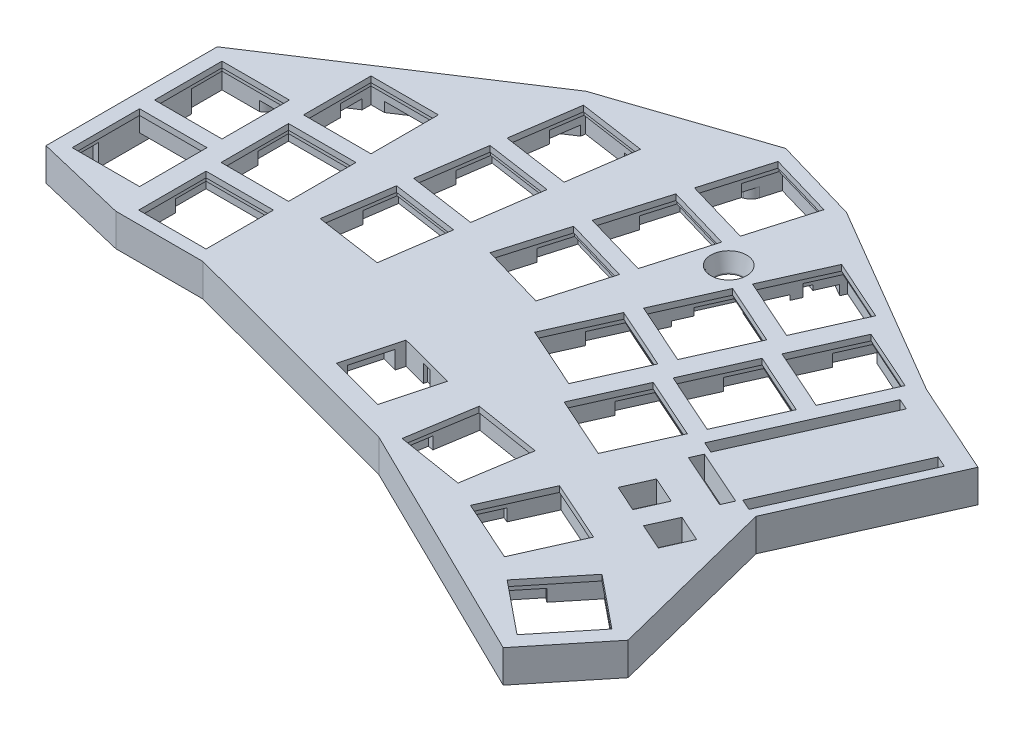
SolidWorks part; units mm, degrees
ref_plane "Front Plane" through (0, 0, 0) normal (0, 0, 1) x (1, 0, 0)
ref_plane "Top Plane" through (0, 0, 0) normal (0, 1, 0) x (1, 0, 0)
ref_plane "Right Plane" through (0, 0, 0) normal (1, 0, 0) x (0, 0, -1)
sketch "Ergogen Drawing" plane through (0, 0, 0) normal (0, 1, 0) x (1, 0, 0)
  line L0 (0.027, 17.9992) -> (18.027, 17.9992)
  line L1 (18.027, 17.9992) -> (18.027, -0.0008)
  line L2 (18.027, -0.0008) -> (0.027, -0.0008)
  line L3 (0.027, -0.0008) -> (0.027, 17.9992)
  line L4 (0.027, 34.9992) -> (18.027, 34.9992)
  line L5 (18.027, 34.9992) -> (18.027, 16.9992)
  line L6 (18.027, 16.9992) -> (0.027, 16.9992)
  line L7 (0.027, 16.9992) -> (0.027, 34.9992)
  line L8 (18.027, 15.9992) -> (36.027, 15.9992)
  line L9 (36.027, 15.9992) -> (36.027, -2.0008)
  line L10 (36.027, -2.0008) -> (18.027, -2.0008)
  line L11 (18.027, -2.0008) -> (18.027, 15.9992)
  line L12 (18.027, 32.9992) -> (36.027, 32.9992)
  line L13 (36.027, 32.9992) -> (36.027, 14.9992)
  line L14 (36.027, 14.9992) -> (18.027, 14.9992)
  line L15 (18.027, 14.9992) -> (18.027, 32.9992)
  line L16 (18.027, 49.9992) -> (36.027, 49.9992)
  line L17 (36.027, 49.9992) -> (36.027, 31.9992)
  line L18 (36.027, 31.9992) -> (18.027, 31.9992)
  line L19 (18.027, 31.9992) -> (18.027, 49.9992)
  line L20 (41.3768, 32.6051) -> (59.3329, 31.3495)
  line L21 (59.3329, 31.3495) -> (58.0773, 13.3933)
  line L22 (58.0773, 13.3933) -> (40.1211, 14.6489)
  line L23 (40.1211, 14.6489) -> (41.3768, 32.6051)
  line L24 (42.5626, 49.5637) -> (60.5188, 48.3081)
  line L25 (60.5188, 48.3081) -> (59.2631, 30.3519)
  line L26 (59.2631, 30.3519) -> (41.307, 31.6075)
  line L27 (41.307, 31.6075) -> (42.5626, 49.5637)
  line L28 (43.7485, 66.5223) -> (61.7046, 65.2667)
  line L29 (61.7046, 65.2667) -> (60.449, 47.3105)
  line L30 (60.449, 47.3105) -> (42.4929, 48.5661)
  line L31 (42.4929, 48.5661) -> (43.7485, 66.5223)
  line L32 (66.0898, 43.7082) -> (83.8507, 40.7838)
  line L33 (83.8507, 40.7838) -> (80.9263, 23.023)
  line L34 (80.9263, 23.023) -> (63.1655, 25.9473)
  line L35 (63.1655, 25.9473) -> (66.0898, 43.7082)
  line L36 (68.8517, 60.4823) -> (86.6126, 57.558)
  line L37 (86.6126, 57.558) -> (83.6882, 39.7971)
  line L38 (83.6882, 39.7971) -> (65.9274, 42.7215)
  line L39 (65.9274, 42.7215) -> (68.8517, 60.4823)
  line L40 (71.6136, 77.2565) -> (89.3745, 74.3321)
  line L41 (89.3745, 74.3321) -> (86.4501, 56.5713)
  line L42 (86.4501, 56.5713) -> (68.6893, 59.4956)
  line L43 (68.6893, 59.4956) -> (71.6136, 77.2565)
  line L44 (88.5581, 32.769) -> (105.9366, 28.0799)
  line L45 (105.9366, 28.0799) -> (101.2475, 10.7014)
  line L46 (101.2475, 10.7014) -> (83.869, 15.3905)
  line L47 (83.869, 15.3905) -> (88.5581, 32.769)
  line L48 (92.9866, 49.182) -> (110.3652, 44.4929)
  line L49 (110.3652, 44.4929) -> (105.6761, 27.1144)
  line L50 (105.6761, 27.1144) -> (88.2976, 31.8035)
  line L51 (88.2976, 31.8035) -> (92.9866, 49.182)
  line L52 (97.4152, 65.595) -> (114.7937, 60.906)
  line L53 (114.7937, 60.906) -> (110.1046, 43.5274)
  line L54 (110.1046, 43.5274) -> (92.7261, 48.2165)
  line L55 (92.7261, 48.2165) -> (97.4152, 65.595)
  line L56 (107.0448, 26.9674) -> (124.0477, 21.0597)
  line L57 (124.0477, 21.0597) -> (118.14, 4.0568)
  line L58 (118.14, 4.0568) -> (101.1371, 9.9645)
  line L59 (101.1371, 9.9645) -> (107.0448, 26.9674)
  line L60 (112.6243, 43.0257) -> (129.6273, 37.118)
  line L61 (129.6273, 37.118) -> (123.7195, 20.1151)
  line L62 (123.7195, 20.1151) -> (106.7166, 26.0228)
  line L63 (106.7166, 26.0228) -> (112.6243, 43.0257)
  line L64 (118.2039, 59.084) -> (135.2068, 53.1763)
  line L65 (135.2068, 53.1763) -> (129.299, 36.1734)
  line L66 (129.299, 36.1734) -> (112.2961, 42.0811)
  line L67 (112.2961, 42.0811) -> (118.2039, 59.084)
  line L68 (95.4197, 6.4051) -> (112.5714, 0.9445)
  line L69 (112.5714, 0.9445) -> (107.1108, -16.2072)
  line L70 (107.1108, -16.2072) -> (89.959, -10.7466)
  line L71 (89.959, -10.7466) -> (95.4197, 6.4051)
  line L72 (116.0129, -0.5249) -> (131.9353, -8.9198)
  line L73 (131.9353, -8.9198) -> (123.5404, -24.8423)
  line L74 (123.5404, -24.8423) -> (107.6179, -16.4473)
  line L75 (107.6179, -16.4473) -> (116.0129, -0.5249)
  line L76 (135.0644, -10.9721) -> (149.2602, -22.0392)
  line L77 (149.2602, -22.0392) -> (138.1931, -36.235)
  line L78 (138.1931, -36.235) -> (123.9973, -25.1679)
  line L79 (123.9973, -25.1679) -> (135.0644, -10.9721)
sketch "Layout Based on OG" plane through (0, 0, 0) normal (0, 1, 0) x (1, 0, 0)
  line L0 (0, 0) -> (0, 17) construction
  line L1 (0, 17) -> (18, 17) construction
  line L2 (18, 17) -> (18, 0) construction
  line L3 (18, 0) -> (0, 0) construction
  line L4 (2.05, 1.55) -> (2.05, 15.45)
  line L5 (2.05, 15.45) -> (15.95, 15.45)
  line L6 (15.95, 15.45) -> (15.95, 1.55)
  line L7 (15.95, 1.55) -> (2.05, 1.55)
  line L8 (109.1798, 58.6066) -> (27, -125.5436) construction
  line L9 (27, 46.7087) -> (27, -125.5436) construction
  line L10 (84.3863, 71.4039) -> (27, -125.5436) construction
  line L11 (54.2678, 62.3831) -> (27, -125.5436) construction
  line L12 (44.7261, 45.0233) -> (58.4821, 43.0274)
  line L13 (2.05, 18.55) -> (15.95, 18.55)
  line L14 (2.05, 18.55) -> (2.05, 32.45)
  line L15 (2.05, 32.45) -> (15.95, 32.45)
  line L16 (15.95, 18.55) -> (15.95, 32.45)
  line L17 (20.05, 31.2587) -> (33.95, 31.2587)
  line L18 (20.05, 31.2587) -> (20.05, 45.1587)
  line L19 (20.05, 45.1587) -> (33.95, 45.1587)
  line L20 (33.95, 31.2587) -> (33.95, 45.1587)
  line L21 (33.95, 28.1587) -> (20.05, 28.1587)
  line L22 (33.95, 28.1587) -> (33.95, 14.2587)
  line L23 (33.95, 14.2587) -> (20.05, 14.2587)
  line L24 (20.05, 28.1587) -> (20.05, 14.2587)
  line L25 (20.05, -2.7413) -> (33.95, -2.7413)
  line L26 (20.05, -2.7413) -> (20.05, 11.1587)
  line L27 (20.05, 11.1587) -> (33.95, 11.1587)
  line L28 (33.95, -2.7413) -> (33.95, 11.1587)
  line L29 (44.7261, 45.0233) -> (42.7302, 31.2674)
  line L30 (58.4821, 43.0274) -> (56.4861, 29.2714)
  line L31 (42.7302, 31.2674) -> (56.4861, 29.2714)
  line L32 (42.285, 28.1995) -> (56.041, 26.2036)
  line L33 (42.285, 28.1995) -> (40.2891, 14.4436)
  line L34 (56.041, 26.2036) -> (54.045, 12.4476)
  line L35 (40.2891, 14.4436) -> (54.045, 12.4476)
  line L36 (47.1672, 61.8472) -> (60.9232, 59.8512)
  line L37 (47.1672, 61.8472) -> (45.1712, 48.0912)
  line L38 (60.9232, 59.8512) -> (58.9272, 46.0953)
  line L39 (45.1712, 48.0912) -> (58.9272, 46.0953)
  line L40 (77.2802, 71.86) -> (90.6252, 67.9716)
  line L41 (77.2802, 71.86) -> (73.3917, 58.515)
  line L42 (90.6252, 67.9716) -> (86.7368, 54.6265)
  line L43 (73.3917, 58.515) -> (86.7368, 54.6265)
  line L44 (85.8695, 51.6503) -> (72.5245, 55.5388)
  line L45 (85.8695, 51.6503) -> (81.9811, 38.3053)
  line L46 (72.5245, 55.5388) -> (68.6361, 42.1937)
  line L47 (81.9811, 38.3053) -> (68.6361, 42.1937)
  line L48 (67.7688, 39.2175) -> (81.1139, 35.329)
  line L49 (67.7688, 39.2175) -> (63.8804, 25.8725)
  line L50 (81.1139, 35.329) -> (77.2254, 21.984)
  line L51 (63.8804, 25.8725) -> (77.2254, 21.984)
  line L52 (102.2015, 60.0235) -> (114.8949, 54.3589)
  line L53 (102.2015, 60.0235) -> (96.5369, 47.3301)
  line L54 (114.8949, 54.3589) -> (109.2302, 41.6655)
  line L55 (96.5369, 47.3301) -> (109.2302, 41.6655)
  line L56 (107.9669, 38.8346) -> (95.2735, 44.4992)
  line L57 (107.9669, 38.8346) -> (102.3023, 26.1412)
  line L58 (95.2735, 44.4992) -> (89.6089, 31.8058)
  line L59 (102.3023, 26.1412) -> (89.6089, 31.8058)
  line L60 (101.039, 23.3103) -> (88.3456, 28.9749)
  line L61 (101.039, 23.3103) -> (95.3744, 10.6169)
  line L62 (88.3456, 28.9749) -> (82.681, 16.2815)
  line L63 (95.3744, 10.6169) -> (82.681, 16.2815)
  line L64 (117.7053, 50.5958) -> (130.3987, 44.9312)
  line L65 (117.7053, 50.5958) -> (112.0407, 37.9024)
  line L66 (130.3987, 44.9312) -> (124.734, 32.2378)
  line L67 (112.0407, 37.9024) -> (124.734, 32.2378)
  line L68 (123.4707, 29.4069) -> (110.7773, 35.0715)
  line L69 (123.4707, 29.4069) -> (117.8061, 16.7135)
  line L70 (110.7773, 35.0715) -> (105.1127, 22.3782)
  line L71 (117.8061, 16.7135) -> (105.1127, 22.3782)
  line L72 (116.5428, 13.8826) -> (103.8494, 19.5473)
  line L73 (116.5428, 13.8826) -> (110.8782, 1.1892)
  line L74 (103.8494, 19.5473) -> (98.1848, 6.8539)
  line L75 (110.8782, 1.1892) -> (98.1848, 6.8539)
  line L76 (90.1692, -2.6429) -> (103.8962, -4.8292)
  line L77 (90.1692, -2.6429) -> (87.9829, -16.3699)
  line L78 (103.8962, -4.8292) -> (101.7099, -18.5562)
  line L79 (87.9829, -16.3699) -> (101.7099, -18.5562)
  line L80 (112.6329, -8.5638) -> (125.3263, -14.2284)
  line L81 (112.6329, -8.5638) -> (106.9683, -21.2572)
  line L82 (125.3263, -14.2284) -> (119.6617, -26.9218)
  line L83 (106.9683, -21.2572) -> (119.6617, -26.9218)
  line L84 (132.8305, -19.9983) -> (143.6253, -28.7552)
  line L85 (132.8305, -19.9983) -> (124.0737, -30.7931)
  line L86 (143.6253, -28.7552) -> (134.8684, -39.55)
  line L87 (124.0737, -30.7931) -> (134.8684, -39.55)
  line L88 (0, 0) -> (0, 34) construction
  line L89 (0, 34) -> (18, 46.7087) construction
  line L90 (18, 46.7087) -> (45.361, 63.6755) construction
  line L91 (45.361, 63.6755) -> (75.7456, 73.9216) construction
  line L92 (75.7456, 73.9216) -> (93.027, 68.8862) construction
  line L93 (93.027, 68.8862) -> (117.3986, 54.9389) construction
  line L94 (117.3986, 54.9389) -> (132.9024, 45.5112) construction
  line L95 (146.1938, -28.843) -> (135.484, -42.0452) construction
  line L96 (135.484, -42.0452) -> (85.7146, -17.5782) construction
  line L97 (0, 0) -> (18, -4.2913) construction
  line L98 (132.9024, 45.5112) -> (119.0465, 14.4627) construction
  line L99 (18, -4.2913) -> (36, -4.2913) construction
  line L100 (36, -4.2913) -> (85.7146, -17.5782) construction
  line L101 (119.0465, 14.4627) -> (137.3104, 6.3121) construction
  line L102 (137.3104, 6.3121) -> (151.1662, 37.3607) construction
  line L103 (151.1662, 37.3607) -> (132.9024, 45.5112) construction
  line L104 (146.1938, -28.843) -> (137.3104, 6.3121) construction
  line L105 (137.3104, 6.3121) -> (151.1662, 37.3607) construction
  line L106 (151.1662, 37.3607) -> (132.9024, 45.5112) construction
  line L107 (119.9597, 14.0551) -> (132.3892, 41.9075)
  line L108 (132.3892, 41.9075) -> (134.6722, 40.8887)
  line L109 (134.6722, 40.8887) -> (122.2427, 13.0363)
  line L110 (122.2427, 13.0363) -> (119.9597, 14.0551)
  line L111 (136.3972, 6.7197) -> (148.8267, 34.5721)
  line L112 (148.8267, 34.5721) -> (146.5437, 35.5909)
  line L113 (146.5437, 35.5909) -> (134.1142, 7.7385)
  line L114 (134.1142, 7.7385) -> (136.3972, 6.7197)
  line L115 (79.4058, -12.7868) -> (67.8127, -9.6883)
  line L116 (67.8127, -9.6883) -> (70.8336, 1.6149)
  line L117 (70.8336, 1.6149) -> (82.4267, -1.4835)
  line L118 (82.4267, -1.4835) -> (79.4058, -12.7868)
  line L119 (97.0327, -3.7361) -> (94.8464, -17.4631) construction
  line L120 (118.9913, -2.8379) -> (121.4364, 2.6412)
  line L121 (121.4364, 2.6412) -> (126.9156, 0.1961)
  line L122 (76.6302, 0.0657) -> (73.6092, -11.2375) construction
  line L123 (126.9156, 0.1961) -> (124.4704, -5.2831)
  line L124 (124.4704, -5.2831) -> (118.9913, -2.8379)
  line L125 (128.4611, -7.064) -> (130.9062, -1.5848)
  line L126 (130.9062, -1.5848) -> (136.3854, -4.03)
  line L127 (136.3854, -4.03) -> (133.9402, -9.5091)
  line L128 (133.9402, -9.5091) -> (128.4611, -7.064)
  line L137 (124.176, 1.4187) -> (121.7308, -4.0605) construction
  line L138 (133.6458, -2.8074) -> (131.2006, -8.2865) construction
  line L139 (126.7317, 7.1456) -> (128.1784, 10.3874) construction
  line L140 (135.0103, 42.8732) -> (147.795, 37.1678) construction
  line L141 (147.795, 37.1678) -> (133.1241, 4.2929) construction
  line L142 (133.1241, 4.2929) -> (120.3393, 9.9982) construction
  line L143 (120.3393, 9.9982) -> (135.0103, 42.8732) construction
  line L144 (120.9329, 9.7333) -> (121.9517, 12.0163)
  line L145 (121.9517, 12.0163) -> (133.5493, 6.8407)
  line L146 (133.5493, 6.8407) -> (132.5305, 4.5578)
  line L147 (132.5305, 4.5578) -> (120.9329, 9.7333)
  line L148 (126.9156, 0.1961) -> (140.3735, -5.8097) construction
  line L164 (-1, 34.5181) -> (-1, -0.7896)
  line L165 (-1, -0.7896) -> (17.8824, -5.2913)
  line L166 (17.8824, -5.2913) -> (35.8687, -5.2913)
  line L167 (35.8687, -5.2913) -> (85.3615, -18.5189)
  line L168 (85.3615, -18.5189) -> (135.7583, -43.2944)
  line L169 (135.7583, -43.2944) -> (147.2861, -29.0838)
  line L170 (147.2861, -29.0838) -> (138.3648, 6.2211)
  line L171 (138.3648, 6.2211) -> (152.487, 37.8664)
  line L172 (152.487, 37.8664) -> (133.3678, 46.3986)
  line L173 (133.3678, 46.3986) -> (117.9068, 55.8002) construction
  line L174 (117.9068, 55.8002) -> (93.4207, 69.8131) construction
  line L175 (93.4207, 69.8131) -> (75.7238, 74.9696)
  line L176 (75.7238, 74.9696) -> (44.9321, 64.5862)
  line L177 (44.9321, 64.5862) -> (17.4476, 47.5429) construction
  line L178 (17.4476, 47.5429) -> (-1, 34.5181) construction
  line L179 (-1, 34.5181) -> (44.9321, 64.5862)
  line L180 (133.3678, 46.3986) -> (93.4207, 69.8131)
  line L181 (27, -125.5436) -> (90.7493, 48.2155) construction
  circle A0 centre (142.6577, -23.0128) radius 2 construction
  circle A1 centre (142.6577, -23.0128) radius 1
  circle A2 centre (99.1237, -21.9416) radius 2 construction
  circle A3 centre (99.1237, -21.9416) radius 1
  circle A6 centre (16.2, -1.8061) radius 2 construction
  circle A7 centre (16.2, -1.8061) radius 1
  circle A8 centre (7.0467, 36.2) radius 2 construction
  circle A9 centre (7.0467, 36.2) radius 1
  circle A10 centre (72.7535, 70.802) radius 2 construction
  circle A11 centre (72.7535, 70.802) radius 1
  circle A12 centre (144.6437, 38.0814) radius 2 construction
  circle A13 centre (144.6437, 38.0814) radius 1
  circle A14 centre (90.7493, 48.2155) radius 3
  point P10 (110.8277, 18.1304)
  point P11 (117.7557, 33.6547)
  point P128 (75.1197, -5.5859)
  point P129 (95.9395, -10.5996)
  point P146 (127.7505, 9.4285)
  point P148 (128.1784, 10.3874)
  point P150 (122.9534, -1.3209)
  point P186 (0, 0)
  line B0 (18, 29.7087) -> (18, 46.7087) construction
  line B1 (18, 46.7087) -> (36, 46.7087) construction
  line B2 (36, 46.7087) -> (36, 29.7087) construction
  line B3 (36, 29.7087) -> (18, 29.7087) construction
  line B4 (20.05, 31.2587) -> (20.05, 45.1587) construction
  line B5 (20.05, 45.1587) -> (33.95, 45.1587) construction
  line B6 (33.95, 45.1587) -> (33.95, 31.2587) construction
  line B7 (33.95, 31.2587) -> (20.05, 31.2587) construction
  line B8 (18, 12.7087) -> (18, 29.7087) construction
  line B9 (18, 29.7087) -> (36, 29.7087) construction
  line B10 (36, 29.7087) -> (36, 12.7087) construction
  line B11 (36, 12.7087) -> (18, 12.7087) construction
  line B12 (20.05, 14.2587) -> (20.05, 28.1587) construction
  line B13 (20.05, 28.1587) -> (33.95, 28.1587) construction
  line B14 (33.95, 28.1587) -> (33.95, 14.2587) construction
  line B15 (33.95, 14.2587) -> (20.05, 14.2587) construction
  line B16 (18, -4.2913) -> (18, 12.7087) construction
  line B17 (18, 12.7087) -> (36, 12.7087) construction
  line B18 (36, 12.7087) -> (36, -4.2913) construction
  line B19 (36, -4.2913) -> (18, -4.2913) construction
  line B20 (20.05, -2.7413) -> (20.05, 11.1587) construction
  line B21 (20.05, 11.1587) -> (33.95, 11.1587) construction
  line B22 (33.95, 11.1587) -> (33.95, -2.7413) construction
  line B23 (33.95, -2.7413) -> (20.05, -2.7413) construction
  line B24 (42.9199, 46.8516) -> (45.361, 63.6755) construction
  line B25 (45.361, 63.6755) -> (63.1745, 61.0908) construction
  line B26 (63.1745, 61.0908) -> (60.7334, 44.267) construction
  line B27 (60.7334, 44.267) -> (42.9199, 46.8516) construction
  line B28 (45.1712, 48.0912) -> (47.1672, 61.8472) construction
  line B29 (47.1672, 61.8472) -> (60.9232, 59.8512) construction
  line B30 (60.9232, 59.8512) -> (58.9272, 46.0953) construction
  line B31 (58.9272, 46.0953) -> (45.1712, 48.0912) construction
  line B32 (40.4788, 30.0278) -> (42.9199, 46.8516) construction
  line B33 (42.9199, 46.8516) -> (60.7334, 44.267) construction
  line B34 (60.7334, 44.267) -> (58.2923, 27.4431) construction
  line B35 (58.2923, 27.4431) -> (40.4788, 30.0278) construction
  line B36 (42.7302, 31.2674) -> (44.7261, 45.0233) construction
  line B37 (44.7261, 45.0233) -> (58.4821, 43.0274) construction
  line B38 (58.4821, 43.0274) -> (56.4861, 29.2714) construction
  line B39 (56.4861, 29.2714) -> (42.7302, 31.2674) construction
  line B40 (38.0377, 13.204) -> (40.4788, 30.0278) construction
  line B41 (40.4788, 30.0278) -> (58.2923, 27.4431) construction
  line B42 (58.2923, 27.4431) -> (55.8512, 10.6193) construction
  line B43 (55.8512, 10.6193) -> (38.0377, 13.204) construction
  line B44 (40.2891, 14.4436) -> (42.285, 28.1995) construction
  line B45 (42.285, 28.1995) -> (56.041, 26.2036) construction
  line B46 (56.041, 26.2036) -> (54.045, 12.4476) construction
  line B47 (54.045, 12.4476) -> (40.2891, 14.4436) construction
  line B48 (70.99, 57.6004) -> (75.7456, 73.9216) construction
  line B49 (75.7456, 73.9216) -> (93.027, 68.8862) construction
  line B50 (93.027, 68.8862) -> (88.2713, 52.5649) construction
  line B51 (88.2713, 52.5649) -> (70.99, 57.6004) construction
  line B52 (73.3917, 58.515) -> (77.2802, 71.86) construction
  line B53 (77.2802, 71.86) -> (90.6252, 67.9716) construction
  line B54 (90.6252, 67.9716) -> (86.7368, 54.6265) construction
  line B55 (86.7368, 54.6265) -> (73.3917, 58.515) construction
  line B56 (66.2343, 41.2791) -> (70.99, 57.6004) construction
  line B57 (70.99, 57.6004) -> (88.2713, 52.5649) construction
  line B58 (88.2713, 52.5649) -> (83.5156, 36.2437) construction
  line B59 (83.5156, 36.2437) -> (66.2343, 41.2791) construction
  line B60 (68.6361, 42.1937) -> (72.5245, 55.5388) construction
  line B61 (72.5245, 55.5388) -> (85.8695, 51.6503) construction
  line B62 (85.8695, 51.6503) -> (81.9811, 38.3053) construction
  line B63 (81.9811, 38.3053) -> (68.6361, 42.1937) construction
  line B64 (61.4786, 24.9578) -> (66.2343, 41.2791) construction
  line B65 (66.2343, 41.2791) -> (83.5156, 36.2437) construction
  line B66 (83.5156, 36.2437) -> (78.76, 19.9224) construction
  line B67 (78.76, 19.9224) -> (61.4786, 24.9578) construction
  line B68 (63.8804, 25.8725) -> (67.7688, 39.2175) construction
  line B69 (67.7688, 39.2175) -> (81.1139, 35.329) construction
  line B70 (81.1139, 35.329) -> (77.2254, 21.984) construction
  line B71 (77.2254, 21.984) -> (63.8804, 25.8725) construction
  line B72 (80.1772, 15.7015) -> (87.1052, 31.2258) construction
  line B73 (87.1052, 31.2258) -> (103.5427, 23.8903) construction
  line B74 (103.5427, 23.8903) -> (96.6147, 8.366) construction
  line B75 (96.6147, 8.366) -> (80.1772, 15.7015) construction
  line B76 (82.681, 16.2815) -> (88.3456, 28.9749) construction
  line B77 (88.3456, 28.9749) -> (101.039, 23.3103) construction
  line B78 (101.039, 23.3103) -> (95.3744, 10.6169) construction
  line B79 (95.3744, 10.6169) -> (82.681, 16.2815) construction
  line B80 (87.1052, 31.2258) -> (94.0331, 46.7501) construction
  line B81 (94.0331, 46.7501) -> (110.4706, 39.4146) construction
  line B82 (110.4706, 39.4146) -> (103.5427, 23.8903) construction
  line B83 (103.5427, 23.8903) -> (87.1052, 31.2258) construction
  line B84 (89.6089, 31.8058) -> (95.2735, 44.4992) construction
  line B85 (95.2735, 44.4992) -> (107.9669, 38.8346) construction
  line B86 (107.9669, 38.8346) -> (102.3023, 26.1412) construction
  line B87 (102.3023, 26.1412) -> (89.6089, 31.8058) construction
  line B88 (94.0331, 46.7501) -> (100.9611, 62.2744) construction
  line B89 (100.9611, 62.2744) -> (117.3986, 54.9389) construction
  line B90 (117.3986, 54.9389) -> (110.4706, 39.4146) construction
  line B91 (110.4706, 39.4146) -> (94.0331, 46.7501) construction
  line B92 (96.5369, 47.3301) -> (102.2015, 60.0235) construction
  line B93 (102.2015, 60.0235) -> (114.8949, 54.3589) construction
  line B94 (114.8949, 54.3589) -> (109.2302, 41.6655) construction
  line B95 (109.2302, 41.6655) -> (96.5369, 47.3301) construction
  line B96 (109.5369, 37.3224) -> (116.4649, 52.8467) construction
  line B97 (116.4649, 52.8467) -> (132.9024, 45.5112) construction
  line B98 (132.9024, 45.5112) -> (125.9744, 29.9869) construction
  line B99 (125.9744, 29.9869) -> (109.5369, 37.3224) construction
  line B100 (112.0407, 37.9024) -> (117.7053, 50.5958) construction
  line B101 (117.7053, 50.5958) -> (130.3987, 44.9312) construction
  line B102 (130.3987, 44.9312) -> (124.734, 32.2378) construction
  line B103 (124.734, 32.2378) -> (112.0407, 37.9024) construction
  line B104 (102.609, 21.7981) -> (109.5369, 37.3224) construction
  line B105 (109.5369, 37.3224) -> (125.9744, 29.9869) construction
  line B106 (125.9744, 29.9869) -> (119.0465, 14.4627) construction
  line B107 (119.0465, 14.4627) -> (102.609, 21.7981) construction
  line B108 (105.1127, 22.3782) -> (110.7773, 35.0715) construction
  line B109 (110.7773, 35.0715) -> (123.4707, 29.4069) construction
  line B110 (123.4707, 29.4069) -> (117.8061, 16.7135) construction
  line B111 (117.8061, 16.7135) -> (105.1127, 22.3782) construction
  line B112 (95.6811, 6.2738) -> (102.609, 21.7981) construction
  line B113 (102.609, 21.7981) -> (119.0465, 14.4627) construction
  line B114 (119.0465, 14.4627) -> (112.1185, -1.0616) construction
  line B115 (112.1185, -1.0616) -> (95.6811, 6.2738) construction
  line B116 (98.1848, 6.8539) -> (103.8494, 19.5473) construction
  line B117 (103.8494, 19.5473) -> (116.5428, 13.8826) construction
  line B118 (116.5428, 13.8826) -> (110.8782, 1.1892) construction
  line B119 (110.8782, 1.1892) -> (98.1848, 6.8539) construction
  line B120 (104.4646, -21.8372) -> (111.3925, -6.3129) construction
  line B121 (111.3925, -6.3129) -> (127.83, -13.6484) construction
  line B122 (127.83, -13.6484) -> (120.9021, -29.1727) construction
  line B123 (120.9021, -29.1727) -> (104.4646, -21.8372) construction
  line B124 (106.9683, -21.2572) -> (112.6329, -8.5638) construction
  line B125 (112.6329, -8.5638) -> (125.3263, -14.2284) construction
  line B126 (125.3263, -14.2284) -> (119.6617, -26.9218) construction
  line B127 (119.6617, -26.9218) -> (106.9683, -21.2572) construction
  line B128 (85.7146, -17.5782) -> (88.3885, -0.7898) construction
  line B129 (88.3885, -0.7898) -> (106.1645, -3.621) construction
  line B130 (106.1645, -3.621) -> (103.4906, -20.4094) construction
  line B131 (103.4906, -20.4094) -> (85.7146, -17.5782) construction
  line B132 (87.9829, -16.3699) -> (90.1692, -2.6429) construction
  line B133 (90.1692, -2.6429) -> (103.8962, -4.8292) construction
  line B134 (103.8962, -4.8292) -> (101.7099, -18.5562) construction
  line B135 (101.7099, -18.5562) -> (87.9829, -16.3699) construction
  line B136 (121.5051, -30.7054) -> (132.215, -17.5031) construction
  line B137 (132.215, -17.5031) -> (146.1938, -28.843) construction
  line B138 (146.1938, -28.843) -> (135.484, -42.0452) construction
  line B139 (135.484, -42.0452) -> (121.5051, -30.7054) construction
  line B140 (124.0737, -30.7931) -> (132.8305, -19.9983) construction
  line B141 (132.8305, -19.9983) -> (143.6253, -28.7552) construction
  line B142 (143.6253, -28.7552) -> (134.8684, -39.55) construction
  line B143 (134.8684, -39.55) -> (124.0737, -30.7931) construction
  line B144 (0, 17) -> (0, 34) construction
  line B145 (0, 34) -> (18, 34) construction
  line B146 (18, 34) -> (18, 17) construction
  line B147 (18, 17) -> (0, 17) construction
  line B148 (2.05, 18.55) -> (2.05, 32.45) construction
  line B149 (2.05, 32.45) -> (15.95, 32.45) construction
  line B150 (15.95, 32.45) -> (15.95, 18.55) construction
  line B151 (15.95, 18.55) -> (2.05, 18.55) construction
  dimension "D46" = 4
  dimension "D47" = 2
  dimension "D48" = 3
  dimension "D52" = 4
  dimension "D53" = 2
  dimension "D54" = 4
  dimension "D55" = 2
  dimension "D57" = 4
  dimension "D58" = 2
  dimension "D60" = 4
  dimension "D61" = 2
  dimension "D63" = 4
  dimension "D64" = 2
  dimension "D51" = 3.85
  dimension "D83" = 6
  dimension "D85" = 3.75
  dimension "D1" = 18
  dimension "D2" = 17
  dimension "D3" = 13.9
  dimension "D4" = 13.9
  dimension "D5" = 2.05
  dimension "D6" = 1.55
  dimension "D7" = 205.1378
  dimension "D8" = 201.6553
  dimension "D9" = 189.8947
  dimension "D10" = 8.256
  dimension "D11" = 15
  dimension "D12" = 15
  dimension "D13" = 1.4278
  dimension "D14" = 0.974
  dimension "D15" = 1.5327
  dimension "D16" = 0.6031
  dimension "D17" = 5.9541
  dimension "D18" = 2.5593
  dimension "D19" = 7.805
  dimension "D20" = 7.989
  dimension "D21" = 172.2524
  dimension "D22" = 2.2911
  dimension "D23" = 4.2913
  dimension "D24" = 34
  dimension "D25" = 20
  dimension "D26" = 30.5
  dimension "D27" = 2.5
  dimension "D28" = 1
  dimension "D29" = 2.5
  dimension "D30" = 30.5
  dimension "D31" = 18
  dimension "D32" = 11.7
  dimension "D33" = 12
  dimension "D34" = 3
  dimension "D35" = 21.415
  dimension "D36" = 6
  dimension "D37" = 6
  dimension "D38" = 6
  dimension "D39" = 6
  dimension "D40" = 14
  dimension "D41" = 36
  dimension "D42" = 12.7
  dimension "D43" = 2.5
  dimension "D44" = 9.27
  dimension "D45" = 4.37
  dimension "D49" = 3.85
  dimension "D50" = 3
  dimension "D56" = 3
  dimension "D59" = 3
  dimension "D62" = 3
  dimension "D65" = 3
  dimension "D66" = 3.75
  dimension "D67" = 1
  dimension "D68" = 1
  dimension "D69" = 1
  dimension "D70" = 1
  dimension "D71" = 1
  dimension "D72" = 1
  dimension "D73" = 1
  dimension "D74" = 1
  dimension "D75" = 1
  dimension "D76" = 1
  dimension "D77" = 1
  dimension "D78" = 1
  dimension "D79" = 1
  dimension "D80" = 1
  dimension "D81" = 1
  dimension "D82" = 3.902
  dimension "D84" = 2.75
sketch_block_instance "Block-ChocSwitchCutout-3"
sketch_block "Block-ChocSwitchCutout" parameters "D1"=18, "D2"=17, "D3"=13.9, "D4"=13.9, "D5"=2.05, "D6"=1.55
sketch_block_instance "Block-ChocSwitchCutout-4"
sketch_block_instance "Block-ChocSwitchCutout-5"
sketch_block_instance "Block-ChocSwitchCutout-6"
sketch_block_instance "Block-ChocSwitchCutout-7"
sketch_block_instance "Block-ChocSwitchCutout-8"
sketch_block_instance "Block-ChocSwitchCutout-9"
sketch_block_instance "Block-ChocSwitchCutout-10"
sketch_block_instance "Block-ChocSwitchCutout-11"
sketch_block_instance "Block-ChocSwitchCutout-20"
sketch_block_instance "Block-ChocSwitchCutout-23"
sketch_block_instance "Block-ChocSwitchCutout-24"
sketch_block_instance "Block-ChocSwitchCutout-27"
sketch_block_instance "Block-ChocSwitchCutout-28"
sketch_block_instance "Block-ChocSwitchCutout-29"
sketch_block_instance "Block-ChocSwitchCutout-32"
sketch_block_instance "Block-ChocSwitchCutout-33"
sketch_block_instance "Block-ChocSwitchCutout-34"
sketch_block_instance "Block-ChocSwitchCutout-37"
other "AlignGroup1"
extrude "Top Plate" add sketch "Layout Based on OG" along normal blind 1.2 contours L105 L106 L94 L93 L92 L91 L90 L89 L88 L97 L99 L100 L96 L95 L104 L73 L75 L74 L72 L69 L71 L70 L68 L61 L63 L62 L60 L57 L59 L58 L56 L45 L47 L46 L44 L6 L7 L4 L5 L16 L13 L14 L15 | A9 | A7 | A3 | A1 | A13 | A11 region at (81.1817, 0, -18.7955) region at (142.6577, 0, 23.0128) region at (99.1237, 0, 21.9416) region at (16.2, 0, 1.8061) region at (7.0467, 0, -36.2) region at (72.7535, 0, -70.802) region at (144.6437, 0, -38.0814)
sketch "Sketch1" plane through (0, 0, 0) normal (0, -1, 0) x (1, 0, 0)
  line L0 (124.9363, -31.7095) -> (130.927, -45.1335)
  line L1 (130.927, -45.1335) -> (117.503, -51.1241)
  line L2 (117.503, -51.1241) -> (111.5124, -37.7002)
  line L3 (111.5124, -37.7002) -> (124.9363, -31.7095)
  line L4 (118.0084, -16.1852) -> (123.999, -29.6092)
  line L5 (117.7053, -50.5958) -> (130.3987, -44.9312) construction
  line L6 (123.999, -29.6092) -> (110.5751, -35.5998)
  line L7 (117.7053, -50.5958) -> (112.0407, -37.9024) construction
  line L8 (110.5751, -35.5998) -> (104.5844, -22.1759)
  line L9 (104.5844, -22.1759) -> (118.0084, -16.1852)
  line L10 (123.4707, -29.4069) -> (117.8061, -16.7135) construction
  line L11 (111.0804, -0.661) -> (117.0711, -14.0849)
  line L12 (117.8061, -16.7135) -> (105.1127, -22.3782) construction
  line L13 (117.0711, -14.0849) -> (103.6471, -20.0755)
  line L14 (103.6471, -20.0755) -> (97.6565, -6.6516)
  line L15 (97.6565, -6.6516) -> (111.0804, -0.661)
  line L16 (103.8494, -19.5473) -> (98.1848, -6.8539) construction
  line L17 (110.8782, -1.1892) -> (98.1848, -6.8539) construction
  line L18 (95.5766, -10.0886) -> (101.5673, -23.5126)
  line L19 (101.5673, -23.5126) -> (88.1433, -29.5032)
  line L20 (88.1433, -29.5032) -> (82.1527, -16.0793)
  line L21 (82.1527, -16.0793) -> (95.5766, -10.0886)
  line L22 (101.039, -23.3103) -> (88.3456, -28.9749) construction
  line L23 (101.039, -23.3103) -> (95.3744, -10.6169) construction
  line L24 (102.5046, -25.6129) -> (108.4952, -39.0369)
  line L25 (108.4952, -39.0369) -> (95.0713, -45.0275)
  line L26 (95.0713, -45.0275) -> (89.0806, -31.6036)
  line L27 (89.0806, -31.6036) -> (102.5046, -25.6129)
  line L28 (102.3023, -26.1412) -> (89.6089, -31.8058) construction
  line L29 (95.2735, -44.4992) -> (89.6089, -31.8058) construction
  line L30 (109.4325, -41.1372) -> (115.4231, -54.5612)
  line L31 (115.4231, -54.5612) -> (101.9992, -60.5518)
  line L32 (101.9992, -60.5518) -> (96.0086, -47.1279)
  line L33 (96.0086, -47.1279) -> (109.4325, -41.1372)
  line L34 (102.2015, -60.0235) -> (114.8949, -54.3589) construction
  line L35 (114.8949, -54.3589) -> (109.2302, -41.6655) construction
  line L36 (119.864, 27.4501) -> (125.8546, 14.0261)
  line L37 (125.8546, 14.0261) -> (112.4307, 8.0355)
  line L38 (112.4307, 8.0355) -> (106.44, 21.4594)
  line L39 (106.44, 21.4594) -> (119.864, 27.4501)
  line L40 (125.3263, 14.2284) -> (119.6617, 26.9218) construction
  line L41 (106.9683, 21.2572) -> (119.6617, 26.9218) construction
  line L42 (144.1879, 28.6966) -> (134.9271, 40.1126)
  line L43 (134.9271, 40.1126) -> (123.511, 30.8517)
  line L44 (123.511, 30.8517) -> (132.7719, 19.4357)
  line L45 (132.7719, 19.4357) -> (144.1879, 28.6966)
  line L46 (143.6253, 28.7552) -> (134.8684, 39.55) construction
  line L47 (132.8305, 19.9983) -> (143.6253, 28.7552) construction
  line L48 (132.8305, 19.9983) -> (124.0737, 30.7931) construction
  line L49 (104.3541, 4.4971) -> (102.042, 19.0142)
  line L50 (102.042, 19.0142) -> (87.5249, 16.702)
  line L51 (87.5249, 16.702) -> (89.8371, 2.185)
  line L52 (89.8371, 2.185) -> (104.3541, 4.4971)
  line L61 (86.3655, -51.9224) -> (82.2532, -37.8093)
  line L62 (103.8962, 4.8292) -> (101.7099, 18.5562) construction
  line L63 (82.2532, -37.8093) -> (68.1401, -41.9216)
  line L64 (87.9829, 16.3699) -> (101.7099, 18.5562) construction
  line L65 (91.1211, -68.2437) -> (87.0089, -54.1306)
  line L66 (87.0089, -54.1306) -> (72.8958, -58.2429)
  line L67 (72.8958, -58.2429) -> (77.008, -72.3559)
  line L68 (77.008, -72.3559) -> (91.1211, -68.2437)
  line L69 (61.3764, -60.1896) -> (59.2656, -45.642)
  line L70 (59.2656, -45.642) -> (44.718, -47.7528)
  line L71 (44.718, -47.7528) -> (46.8288, -62.3005)
  line L72 (46.8288, -62.3005) -> (61.3764, -60.1896)
  line L73 (34.35, -45.5587) -> (34.35, -30.8587)
  line L74 (34.35, -30.8587) -> (19.65, -30.8587)
  line L75 (19.65, -30.8587) -> (19.65, -45.5587)
  line L76 (19.65, -45.5587) -> (34.35, -45.5587)
  line L77 (90.6252, -67.9716) -> (86.7368, -54.6265) construction
  line L78 (47.1672, -61.8472) -> (45.1712, -48.0912) construction
  line L79 (33.95, -31.2587) -> (33.95, -45.1587) construction
  line L80 (73.3917, -58.515) -> (86.7368, -54.6265) construction
  line L81 (60.9232, -59.8512) -> (58.9272, -46.0953) construction
  line L82 (45.1712, -48.0912) -> (58.9272, -46.0953) construction
  line L83 (68.1401, -41.9216) -> (72.2524, -56.0347)
  line L84 (20.05, -31.2587) -> (33.95, -31.2587) construction
  line L85 (72.2524, -56.0347) -> (86.3655, -51.9224)
  line L86 (85.8695, -51.6503) -> (81.9811, -38.3053) construction
  line L87 (81.9811, -38.3053) -> (68.6361, -42.1937) construction
  line L88 (81.6098, -35.6012) -> (77.4976, -21.4881)
  line L89 (77.4976, -21.4881) -> (63.3845, -25.6003)
  line L90 (63.3845, -25.6003) -> (67.4967, -39.7134)
  line L91 (67.4967, -39.7134) -> (81.6098, -35.6012)
  line L92 (81.1139, -35.329) -> (77.2254, -21.984) construction
  line L93 (63.8804, -25.8725) -> (77.2254, -21.984) construction
  line L94 (58.9353, -43.3658) -> (56.8245, -28.8181)
  line L95 (56.8245, -28.8181) -> (42.2769, -30.929)
  line L96 (42.2769, -30.929) -> (44.3877, -45.4766)
  line L97 (44.3877, -45.4766) -> (58.9353, -43.3658)
  line L98 (58.4821, -43.0274) -> (56.4861, -29.2714) construction
  line L99 (42.7302, -31.2674) -> (56.4861, -29.2714) construction
  line L100 (56.4943, -26.542) -> (54.3834, -11.9943)
  line L101 (54.3834, -11.9943) -> (39.8358, -14.1052)
  line L102 (39.8358, -14.1052) -> (41.9466, -28.6528)
  line L103 (41.9466, -28.6528) -> (56.4943, -26.542)
  line L104 (56.041, -26.2036) -> (54.045, -12.4476) construction
  line L105 (40.2891, -14.4436) -> (54.045, -12.4476) construction
  line L106 (34.35, -28.5587) -> (34.35, -13.8587)
  line L107 (34.35, -13.8587) -> (19.65, -13.8587)
  line L108 (19.65, -13.8587) -> (19.65, -28.5587)
  line L109 (19.65, -28.5587) -> (34.35, -28.5587)
  line L110 (33.95, -28.1587) -> (33.95, -14.2587) construction
  line L111 (33.95, -14.2587) -> (20.05, -14.2587) construction
  line L112 (34.35, -11.5587) -> (34.35, 3.1413)
  line L113 (34.35, 3.1413) -> (19.65, 3.1413)
  line L114 (19.65, 3.1413) -> (19.65, -11.5587)
  line L115 (19.65, -11.5587) -> (34.35, -11.5587)
  line L116 (20.05, 2.7413) -> (33.95, 2.7413) construction
  line L117 (20.05, 2.7413) -> (20.05, -11.1587) construction
  line L118 (16.35, -15.85) -> (16.35, -1.15)
  line L119 (16.35, -1.15) -> (1.65, -1.15)
  line L120 (1.65, -1.15) -> (1.65, -15.85)
  line L121 (1.65, -15.85) -> (16.35, -15.85)
  line L122 (2.05, -1.55) -> (2.05, -15.45) construction
  line L123 (15.95, -1.55) -> (2.05, -1.55) construction
  line L124 (16.35, -32.85) -> (16.35, -18.15)
  line L125 (16.35, -18.15) -> (1.65, -18.15)
  line L126 (1.65, -18.15) -> (1.65, -32.85)
  line L127 (1.65, -32.85) -> (16.35, -32.85)
  line L128 (2.05, -18.55) -> (2.05, -32.45) construction
  line L129 (2.05, -18.55) -> (15.95, -18.55) construction
  dimension "D1" = 14.7
  dimension "D2" = 14.7
  dimension "D3" = 0.4
  dimension "D4" = 0.4
  dimension "D5" = 14.7
  dimension "D6" = 14.7
  dimension "D7" = 0.4
  dimension "D8" = 0.4
  dimension "D9" = 14.7
  dimension "D10" = 14.7
  dimension "D11" = 0.4
  dimension "D12" = 0.4
  dimension "D13" = 14.7
  dimension "D14" = 14.7
  dimension "D15" = 0.4
  dimension "D16" = 0.4
  dimension "D17" = 14.7
  dimension "D18" = 14.7
  dimension "D19" = 0.4
  dimension "D20" = 0.4
  dimension "D21" = 14.7
  dimension "D22" = 0.4
  dimension "D23" = 0.4
  dimension "D24" = 14.7
  dimension "D25" = 14.7
  dimension "D26" = 14.7
  dimension "D27" = 0.4
  dimension "D28" = 0.4
  dimension "D29" = 14.7
  dimension "D30" = 14.7
  dimension "D31" = 0.4
  dimension "D32" = 0.4
  dimension "D33" = 14.7
  dimension "D34" = 14.7
  dimension "D35" = 0.4
  dimension "D36" = 0.4
  dimension "D37" = 0.4
  dimension "D38" = 0.4
  dimension "D39" = 14.7
  dimension "D40" = 14.7
  dimension "D41" = 0.4
  dimension "D42" = 0.4
  dimension "D43" = 14.7
  dimension "D44" = 14.7
  dimension "D45" = 14.7
  dimension "D46" = 0.4
  dimension "D47" = 0.4
  dimension "D48" = 14.7
  dimension "D49" = 14.7
  dimension "D50" = 14.7
  dimension "D51" = 0.4
  dimension "D52" = 0.4
  dimension "D53" = 14.7
  dimension "D54" = 14.7
  dimension "D55" = 0.4
  dimension "D56" = 0.4
  dimension "D57" = 14.7
  dimension "D58" = 14.7
  dimension "D59" = 0.4
  dimension "D60" = 0.4
  dimension "D61" = 14.7
  dimension "D62" = 14.7
  dimension "D63" = 0.4
  dimension "D64" = 0.4
  dimension "D65" = 14.7
  dimension "D66" = 14.7
  dimension "D67" = 0.4
  dimension "D68" = 0.4
  dimension "D69" = 14.7
  dimension "D70" = 14.7
  dimension "D71" = 0.4
  dimension "D72" = 0.4
  dimension "D73" = 14.7
  dimension "D74" = 14.7
  dimension "D75" = 0.4
  dimension "D76" = 0.4
  dimension "D77" = 14.7
  dimension "D78" = 14.7
  dimension "D79" = 0.4
  dimension "D80" = 0.4
extrude "Boss-Extrude2" add sketch "Layout Based on OG<7>" against normal blind 5.5 contours L172 L180 L175 L176 L179 L164 L165 L166 L167 L168 L169 L170 L171 A13 A11 A9 A7 A3 A1 L146 L147 L144 L145 L127 L128 L125 L126 L123 L124 L120 L121 L117 L118 L115 L116 L109 L110 L107 L108 region at (81.1817, 0, -18.7955)
sketch "Layout Based on OG<7>" plane through (0, 0, 0) normal (0, 1, 0) x (1, 0, 0) same geometry as "Layout Based on OG"
extrude "Cut-Extrude1" cut sketch "Sketch1" along normal blind 5.5
sketch "Sketch4" plane through (0, -5.5, 0) normal (0, -1, 0) x (1, 0, 0)
  line L0 (74.3817, 12.2203) -> (77.7899, -0.5321)
  line L1 (77.7899, -0.5321) -> (75.8577, -1.0485)
  line L2 (75.8577, -1.0485) -> (72.4495, 11.7039)
  line L3 (72.4495, 11.7039) -> (74.3817, 12.2203)
  line L4 (67.8127, 9.6883) -> (70.8336, -1.6149) construction
  line L6 (79.4058, 12.7868) -> (67.8127, 9.6883) construction
  line L8 (82.4267, 1.4835) -> (79.4058, 12.7868) construction
  line L9 (83.0232, 11.8386) -> (85.0888, 4.1099)
  line L10 (85.0888, 4.1099) -> (76.394, 1.7861)
  line L11 (76.394, 1.7861) -> (67.2162, -0.6668)
  line L12 (67.2162, -0.6668) -> (65.1505, 7.0619)
  line L14 (83.0232, 11.8386) -> (74.3284, 9.5148)
  line L15 (74.3284, 9.5148) -> (65.1505, 7.0619)
  dimension "D1" = 2
  dimension "D2" = 13.2
  dimension "D3" = 0.75
  dimension "D4" = 5
  dimension "D5" = 9
  dimension "D6" = 9.5
  dimension "D7" = 3.25
  dimension "D8" = 8
  dimension "D9" = 1.85
  dimension "D10" = 9
extrude "Cut-Extrude2" cut sketch "Sketch4" against normal blind 5.7 contours L9 L14 L0 L10 | L2 L15 L12 L11 | L10 L11 L2 L1 L0 | L15 L14 L0 L3 L2 region at (73.7512, -5.5, 10.7062) region at (80.0709, -5.5, 6.9092) region at (76.4882, -5.5, 0.4656) region at (70.1685, -5.5, 4.2626)
sketch "Sketch5" plane through (0, -5.5, 0) normal (0, -1, 0) x (1, 0, 0)
  line L0 (90.4768, -61.9215) -> (92.5469, -69.0261)
  line L1 (92.5469, -69.0261) -> (76.2257, -73.7817)
  line L2 (76.2257, -73.7817) -> (74.1556, -66.6772)
  line L3 (74.1556, -66.6772) -> (90.4768, -61.9215)
  line L4 (91.1211, -68.2437) -> (87.0089, -54.1306) construction
  line L5 (80.9655, -29.279) -> (83.0356, -36.3835)
  line L6 (83.0356, -36.3835) -> (66.7143, -41.1392)
  line L7 (66.7143, -41.1392) -> (64.6442, -34.0347)
  line L8 (64.6442, -34.0347) -> (80.9655, -29.279)
  line L9 (72.2524, -56.0347) -> (86.3655, -51.9224) construction
  line L10 (77.008, -72.3559) -> (91.1211, -68.2437) construction
  line L11 (85.7211, -45.6003) -> (87.7913, -52.7048)
  line L12 (87.7913, -52.7048) -> (71.47, -57.4605)
  line L13 (71.47, -57.4605) -> (69.3999, -50.3559)
  line L14 (69.3999, -50.3559) -> (85.7211, -45.6003)
  line L15 (68.1401, -41.9216) -> (72.2524, -56.0347) construction
  line L16 (81.6098, -35.6012) -> (77.4976, -21.4881) construction
  line L17 (67.4967, -39.7134) -> (81.6098, -35.6012) construction
  line L18 (113.9263, -48.385) -> (116.942, -55.1427)
  line L19 (116.942, -55.1427) -> (101.4177, -62.0706)
  line L20 (101.4177, -62.0706) -> (98.402, -55.313)
  line L21 (98.402, -55.313) -> (113.9263, -48.385)
  line L22 (96.0086, -47.1279) -> (101.9992, -60.5518) construction
  line L23 (106.9983, -32.8608) -> (110.014, -39.6184)
  line L24 (110.014, -39.6184) -> (94.4897, -46.5463)
  line L25 (94.4897, -46.5463) -> (91.474, -39.7887)
  line L26 (91.474, -39.7887) -> (106.9983, -32.8608)
  line L27 (100.0704, -17.3365) -> (103.0861, -24.0941)
  line L28 (103.0861, -24.0941) -> (87.5618, -31.022)
  line L29 (87.5618, -31.022) -> (84.5461, -24.2644)
  line L30 (84.5461, -24.2644) -> (100.0704, -17.3365)
  line L31 (115.5742, -7.9088) -> (118.5899, -14.6664)
  line L32 (118.5899, -14.6664) -> (103.0656, -21.5944)
  line L33 (103.0656, -21.5944) -> (100.0499, -14.8367)
  line L34 (100.0499, -14.8367) -> (115.5742, -7.9088)
  line L35 (122.5021, -23.4331) -> (125.5178, -30.1907)
  line L36 (125.5178, -30.1907) -> (109.9935, -37.1187)
  line L37 (109.9935, -37.1187) -> (106.9778, -30.361)
  line L38 (106.9778, -30.361) -> (122.5021, -23.4331)
  line L39 (129.4301, -38.9574) -> (132.4458, -45.715)
  line L40 (132.4458, -45.715) -> (116.9215, -52.6429)
  line L41 (116.9215, -52.6429) -> (113.9058, -45.8853)
  line L42 (113.9058, -45.8853) -> (129.4301, -38.9574)
  line L43 (130.927, -45.1335) -> (124.9363, -31.7095) construction
  line L44 (117.503, -51.1241) -> (130.927, -45.1335) construction
  line L45 (115.4231, -54.5612) -> (109.4325, -41.1372) construction
  line L46 (101.9992, -60.5518) -> (115.4231, -54.5612) construction
  line L47 (89.0806, -31.6036) -> (95.0713, -45.0275) construction
  line L48 (95.0713, -45.0275) -> (108.4952, -39.0369) construction
  line L49 (88.1433, -29.5032) -> (101.5673, -23.5126) construction
  line L50 (101.5673, -23.5126) -> (95.5766, -10.0886) construction
  line L51 (117.0711, -14.0849) -> (111.0804, -0.661) construction
  line L52 (103.6471, -20.0755) -> (117.0711, -14.0849) construction
  line L53 (123.999, -29.6092) -> (118.0084, -16.1852) construction
  line L54 (110.5751, -35.5998) -> (123.999, -29.6092) construction
  line L55 (61.6171, -53.8393) -> (62.6797, -61.1626)
  line L56 (62.6797, -61.1626) -> (45.8558, -63.6037)
  line L57 (45.8558, -63.6037) -> (44.7932, -56.2804)
  line L58 (44.7932, -56.2804) -> (61.6171, -53.8393)
  line L59 (61.3764, -60.1896) -> (59.2656, -45.642) construction
  line L60 (59.176, -37.0154) -> (60.2386, -44.3387)
  line L61 (60.2386, -44.3387) -> (43.4147, -46.7798)
  line L62 (43.4147, -46.7798) -> (42.3521, -39.4565)
  line L63 (42.3521, -39.4565) -> (59.176, -37.0154)
  line L64 (56.7349, -20.1916) -> (57.7975, -27.5149)
  line L65 (57.7975, -27.5149) -> (40.9736, -29.956)
  line L66 (40.9736, -29.956) -> (39.911, -22.6327)
  line L67 (39.911, -22.6327) -> (56.7349, -20.1916)
  line L68 (35.5, -39.3087) -> (35.5, -46.7087)
  line L69 (35.5, -46.7087) -> (18.5, -46.7087)
  line L70 (18.5, -46.7087) -> (18.5, -39.3087)
  line L71 (18.5, -39.3087) -> (35.5, -39.3087)
  line L72 (34.35, -45.5587) -> (34.35, -30.8587) construction
  line L73 (35.5, -22.3087) -> (35.5, -29.7087)
  line L74 (35.5, -29.7087) -> (18.5, -29.7087)
  line L75 (18.5, -29.7087) -> (18.5, -22.3087)
  line L76 (18.5, -22.3087) -> (35.5, -22.3087)
  line L77 (17.5, -26.6) -> (17.5, -34)
  line L78 (17.5, -34) -> (0.5, -34)
  line L79 (0.5, -34) -> (0.5, -26.6)
  line L80 (0.5, -26.6) -> (17.5, -26.6)
  line L81 (17.5, 0) -> (17.5, -7.4)
  line L82 (17.5, -7.4) -> (0.5, -7.4)
  line L83 (0.5, -7.4) -> (0.5, 0)
  line L84 (0.5, 0) -> (17.5, 0)
  line L85 (35.5, -5.3087) -> (35.5, -12.7087)
  line L86 (35.5, -12.7087) -> (18.5, -12.7087)
  line L87 (18.5, -12.7087) -> (18.5, -5.3087)
  line L88 (18.5, -5.3087) -> (35.5, -5.3087)
  line L89 (46.8288, -62.3005) -> (61.3764, -60.1896) construction
  line L90 (58.9353, -43.3658) -> (56.8245, -28.8181) construction
  line L91 (44.3877, -45.4766) -> (58.9353, -43.3658) construction
  line L92 (41.9466, -28.6528) -> (56.4943, -26.542) construction
  line L93 (39.8358, -14.1052) -> (41.9466, -28.6528) construction
  line L94 (19.65, -45.5587) -> (34.35, -45.5587) construction
  line L95 (19.65, -30.8587) -> (19.65, -45.5587) construction
  line L96 (19.65, -28.5587) -> (34.35, -28.5587) construction
  line L97 (34.35, -28.5587) -> (34.35, -13.8587) construction
  line L98 (19.65, -11.5587) -> (34.35, -11.5587) construction
  line L99 (19.65, 3.1413) -> (19.65, -11.5587) construction
  line L101 (1.65, -1.15) -> (1.65, -15.85) construction
  line L102 (1.65, -32.85) -> (16.35, -32.85) construction
  line L103 (1.65, -18.15) -> (1.65, -32.85) construction
  line L104 (120.4455, 28.9689) -> (123.4612, 22.2113)
  line L105 (123.4612, 22.2113) -> (107.9369, 15.2833)
  line L106 (107.9369, 15.2833) -> (104.9212, 22.0409)
  line L107 (104.9212, 22.0409) -> (120.4455, 28.9689)
  line L108 (102.9968, 20.3307) -> (104.1607, 13.0228)
  line L109 (104.1607, 13.0228) -> (87.3723, 10.3489)
  line L110 (87.3723, 10.3489) -> (86.2084, 17.6568)
  line L111 (86.2084, 17.6568) -> (102.9968, 20.3307)
  line L112 (135.0957, 41.7302) -> (139.7576, 35.9834)
  line L113 (139.7576, 35.9834) -> (126.5554, 25.2735)
  line L114 (126.5554, 25.2735) -> (121.8934, 31.0203)
  line L115 (121.8934, 31.0203) -> (135.0957, 41.7302)
  line L116 (87.5249, 16.702) -> (89.8371, 2.185) construction
  line L117 (123.511, 30.8517) -> (132.7719, 19.4357) construction
  line L118 (106.44, 21.4594) -> (112.4307, 8.0355) construction
  line L119 (102.042, 19.0142) -> (87.5249, 16.702) construction
  line L120 (119.864, 27.4501) -> (106.44, 21.4594) construction
  line L121 (134.9271, 40.1126) -> (123.511, 30.8517) construction
  line L122 (16.35, -1.15) -> (1.65, -1.15) construction
  point P156 (106.429, 18.6621)
  dimension "D1" = 17
  dimension "D2" = 7.4
  dimension "D3" = 1.15
  dimension "D4" = 1.15
  dimension "D5" = 17
  dimension "D6" = 7.4
  dimension "D7" = 17
  dimension "D8" = 7.4
  dimension "D9" = 1.15
  dimension "D10" = 1.15
  dimension "D11" = 1.15
  dimension "D12" = 1.15
  dimension "D13" = 17
  dimension "D14" = 7.4
  dimension "D15" = 17
  dimension "D16" = 7.4
  dimension "D17" = 17
  dimension "D18" = 7.4
  dimension "D19" = 17
  dimension "D20" = 7.4
  dimension "D21" = 17
  dimension "D22" = 7.4
  dimension "D23" = 17
  dimension "D24" = 7.4
  dimension "D25" = 1.15
  dimension "D26" = 1.15
  dimension "D27" = 1.15
  dimension "D28" = 1.15
  dimension "D29" = 1.15
  dimension "D30" = 1.15
  dimension "D31" = 1.15
  dimension "D32" = 1.15
  dimension "D33" = 1.15
  dimension "D34" = 1.15
  dimension "D35" = 1.15
  dimension "D36" = 1.15
  dimension "D37" = 17
  dimension "D38" = 7.4
  dimension "D39" = 17
  dimension "D40" = 7.4
  dimension "D41" = 17
  dimension "D42" = 7.4
  dimension "D43" = 17
  dimension "D44" = 7.4
  dimension "D45" = 17
  dimension "D46" = 7.4
  dimension "D47" = 17
  dimension "D48" = 7.4
  dimension "D49" = 17
  dimension "D50" = 7.4
  dimension "D51" = 17
  dimension "D52" = 7.4
  dimension "D53" = 1.15
  dimension "D54" = 1.15
  dimension "D55" = 1.15
  dimension "D56" = 1.15
  dimension "D57" = 1.15
  dimension "D58" = 1.15
  dimension "D59" = 1.15
  dimension "D60" = 1.15
  dimension "D61" = 1.15
  dimension "D62" = 1.15
  dimension "D63" = 1.15
  dimension "D64" = 1.15
  dimension "D65" = 1.15
  dimension "D66" = 1.15
  dimension "D67" = 1.15
  dimension "D68" = 1.15
  dimension "D69" = 17
  dimension "D70" = 7.4
  dimension "D71" = 17
  dimension "D72" = 7.4
  dimension "D73" = 17
  dimension "D74" = 7.4
  dimension "D75" = 1.15
  dimension "D76" = 1.15
  dimension "D77" = 1.15
  dimension "D78" = 1.15
  dimension "D79" = 1.15
  dimension "D80" = 1.15
extrude "Cut-Extrude3" cut sketch "Sketch5" against normal blind 4.5
sketch "Sketch6" plane through (0, -5.5, 0) normal (0, -1, 0) x (1, 0, 0)
  line L0 (137.2986, 4.4375) -> (129.993, 1.1773)
  line L1 (129.993, 1.1773) -> (127.5479, 6.6564)
  line L2 (127.5479, 6.6564) -> (134.8534, 9.9166)
  line L3 (134.8534, 9.9166) -> (137.2986, 4.4375)
  line L4 (125.3836, 5.6906) -> (127.8288, 0.2114)
  line L5 (127.8288, 0.2114) -> (120.5232, -3.0488)
  line L6 (120.5232, -3.0488) -> (118.0781, 2.4304)
  line L7 (118.0781, 2.4304) -> (125.3836, 5.6906)
  line L8 (130.9062, 1.5848) -> (136.3854, 4.03) construction
  line L9 (121.4364, -2.6412) -> (126.9156, -0.1961) construction
  line L10 (133.9402, 9.5091) -> (128.4611, 7.064) construction
  line L11 (124.4704, 5.2831) -> (118.9913, 2.8379) construction
  point P10 (133.6458, 2.8074)
  point P11 (133.6458, 2.8074)
  point P14 (124.176, -1.4187)
  point P15 (124.176, -1.4187)
  dimension "D1" = 8
  dimension "D2" = 8
extrude "Cut-Extrude4" cut sketch "Sketch6" against normal blind 2.2
sketch "Sketch8" plane through (0, -5.5, 0) normal (0, -1, 0) x (1, 0, 0)
  line L0 (139.2044, 23.1731) -> (142.6548, 18.9197)
  line L1 (148.8267, -34.5721) -> (136.2559, -6.4032)
  line L2 (136.2559, -6.4032) -> (142.6548, 18.9197)
  line L3 (148.8267, -34.5721) -> (146.5437, -35.5909)
  line L4 (141.5212, -37.8323) -> (131.0194, -42.5188)
  line L5 (132.4458, -45.715) -> (129.4301, -38.9574) construction
  line L6 (100.9102, -60.9335) -> (116.4345, -54.0056)
  line L7 (1.65, -32.85) -> (1.65, -34)
  line L8 (116.942, -55.1427) -> (113.9263, -48.385) construction
  line L9 (0, -34) -> (18, -34) construction
  line L10 (116.4345, -54.0056) -> (116.9215, -52.6429)
  line L11 (98.402, -55.313) -> (101.4177, -62.0706) construction
  line L12 (100.9102, -60.9335) -> (91.7529, -66.301)
  line L13 (92.5469, -69.0261) -> (90.4768, -61.9215) construction
  line L14 (91.7529, -66.301) -> (75.4316, -71.0566)
  line L15 (74.1556, -66.6772) -> (76.2257, -73.7817) construction
  line L16 (75.4316, -71.0566) -> (75.1536, -70.1026)
  line L17 (73.5523, -68.433) -> (55.2073, -62.2468)
  line L18 (45.361, -63.6755) -> (63.1745, -61.0908) construction
  line L19 (55.2073, -62.2468) -> (45.7271, -62.7161)
  line L20 (44.7932, -56.2804) -> (45.8558, -63.6037) construction
  line L21 (45.7271, -62.7161) -> (21.2741, -46.7087)
  line L22 (18, -46.7087) -> (36, -46.7087) construction
  line L23 (21.2741, -46.7087) -> (18.5, -44.8928)
  line L24 (18.5, -39.3087) -> (18.5, -46.7087) construction
  line L25 (18.5, -44.8928) -> (8.4161, -38.2916)
  line L26 (138.4799, 24.0661) -> (131.9975, 39.2169)
  line L27 (133.3678, -46.3986) -> (93.4207, -69.8131) construction
  line L28 (113.9058, -45.8853) -> (116.9215, -52.6429) construction
  line L29 (116.9215, -52.6429) -> (131.0194, -42.5188)
  line L30 (100.9611, -62.2744) -> (117.3986, -54.9389) construction
  line L31 (1.65, -32.85) -> (1.65, -0.6347)
  line L32 (135.7583, 43.2944) -> (147.2861, 29.0838) construction
  line L33 (136.3972, -6.7197) -> (148.8267, -34.5721) construction
  line L34 (147.2861, 29.0838) -> (138.3648, -6.2211) construction
  line L35 (91.1211, -68.2437) -> (77.008, -72.3559) construction
  line L36 (75.7238, -74.9696) -> (44.9321, -64.5862) construction
  line L37 (-1, -34.5181) -> (44.9321, -64.5862) construction
  line L38 (1.65, -0.6347) -> (19.65, -0.6347)
  line L39 (19.65, 3.1413) -> (19.65, -11.5587) construction
  line L40 (131.9975, 39.2169) -> (100.7388, 23.8499)
  line L41 (129.6887, 11.6745) -> (123.8717, 9.0785) construction
  line L42 (35.5701, 3.1413) -> (86.3584, 16.7151)
  line L43 (86.2084, 17.6568) -> (87.3723, 10.3489) construction
  line L44 (-1, 0.7896) -> (17.8824, 5.2913) construction
  line L45 (130.5038, 9.8481) -> (124.6867, 7.2522)
  line L46 (35.8687, 5.2913) -> (85.3615, 18.5189) construction
  line L47 (34.35, 3.1413) -> (35.5701, 3.1413)
  line L48 (34.35, 3.1413) -> (19.65, 3.1413) construction
  line L49 (135.484, 42.0452) -> (121.5051, 30.7054) construction
  line L50 (85.3615, 18.5189) -> (135.7583, 43.2944) construction
  line L51 (1.65, -34) -> (8.2342, -34)
  line L52 (139.2044, 23.1731) -> (138.4799, 24.0661)
  line L53 (132.7719, 19.4357) -> (144.1879, 28.6966) construction
  line L54 (86.3584, 16.7151) -> (100.6424, 19.9557)
  line L55 (103.4906, 20.4094) -> (85.7146, 17.5782) construction
  line L56 (128.8737, 13.5009) -> (123.0566, 10.9049)
  line L63 (86.1692, -6.3146) -> (62.3834, -12.6717) construction
  line L64 (86.8147, -8.7299) -> (63.0289, -15.0869)
  line L65 (85.5237, -3.8994) -> (61.7379, -10.2565)
  line L66 (66.4366, -56.1669) -> (64.0032, -44.9546) construction
  line L67 (64.9707, -56.485) -> (62.5373, -45.2727)
  line L68 (67.9025, -55.8488) -> (65.4691, -44.6364)
  line L69 (39.9198, -53.3451) -> (39.4405, -46.7087) construction
  line L70 (38.4237, -53.4532) -> (37.9444, -46.8168)
  line L71 (41.4159, -53.2371) -> (40.9366, -46.6007)
  line L75 (133.9402, 9.5091) -> (128.4611, 7.064) construction
  line L76 (126.7317, -7.1456) -> (128.1784, -10.3874) construction
  line L77 (133.6458, 2.8074) -> (131.2006, 8.2865) construction
  line L78 (127.8288, 0.2114) -> (125.3836, 5.6906) construction
  line L79 (112.4307, 8.0355) -> (125.8546, 14.0261) construction
  line L85 (68.1401, -41.9216) -> (70.504, -50.0342) construction
  line L87 (44.718, -47.7528) -> (45.9313, -56.1152) construction
  line L88 (121.9517, -12.0163) -> (133.5493, -6.8407) construction
  line L91 (72.2524, -56.0347) -> (86.3655, -51.9224) construction
  line L92 (34.35, 3.1413) -> (19.65, -0.6347)
  line L93 (59.2656, -45.642) -> (44.718, -47.7528) construction
  circle A0 centre (136.6619, -29.3973) radius 2.5
  arc A1 (8.4161, -38.2916) -> (8.2342, -34) centre (7.0467, -36.2) ccw
  arc A2 (75.1536, -70.1026) -> (73.5523, -68.433) centre (72.7535, -70.802) ccw
  arc A3 (146.5437, -35.5909) -> (141.5212, -37.8323) centre (144.6437, -38.0814) ccw
  arc A5 (100.6424, 19.9557) -> (100.7388, 23.8499) centre (99.1237, 21.9416) ccw
  circle A6 centre (131.6966, -18.271) radius 2.5
  circle A8 centre (109.5914, 3.3881) radius 3.4349 construction
  arc A9 (130.5038, 9.8481) -> (128.8737, 13.5009) centre (129.6887, 11.6745) ccw
  arc A10 (123.0566, 10.9049) -> (124.6867, 7.2522) centre (123.8717, 9.0785) ccw
  arc A15 (86.8147, -8.7299) -> (85.5237, -3.8994) centre (86.1692, -6.3146) ccw
  arc A16 (61.7379, -10.2565) -> (63.0289, -15.0869) centre (62.3834, -12.6717) ccw
  arc A17 (64.9707, -56.485) -> (67.9025, -55.8488) centre (66.4366, -56.1669) ccw
  arc A18 (65.4691, -44.6364) -> (62.5373, -45.2727) centre (64.0032, -44.9546) ccw
  arc A19 (38.4237, -53.4532) -> (41.4159, -53.2371) centre (39.9198, -53.3451) ccw
  arc A20 (40.9366, -46.6007) -> (37.9444, -46.8168) centre (39.4405, -46.7087) ccw
  circle A23 centre (109.5914, 3.3881) radius 2.25
  point P109 (126.7802, 10.3765)
  point P128 (74.2763, -9.4932)
  point P135 (65.2199, -50.5607)
  point P142 (39.6801, -50.0269)
  dimension "D7" = 5
  dimension "D8" = 5
  dimension "D9" = 4.5
  dimension "D10" = 5
  dimension "D11" = 5
  dimension "D12" = 5
  dimension "D13" = 2.5
  dimension "D15" = 2
  dimension "D21" = 1.5
  dimension "D22" = 1.5
  dimension "D27" = 4
  dimension "D1" = 2
  dimension "D2" = 2
  dimension "D3" = 2
  dimension "D4" = 2
  dimension "D5" = 2
  dimension "D6" = 2
  dimension "D17" = 4
  dimension "D18" = 4.125
  dimension "D23" = 3.75
  dimension "D26" = 8
  dimension "D28" = 7.75
  dimension "D29" = 3.71
  dimension "D30" = 9.683
  dimension "D31" = 9.683
extrude "Cut-Extrude5" cut sketch "Sketch8" against normal blind 2
fillet "Fillet1" radius 1.5 19 edges at (38.184, -3.5, -50.135) (40.0278, -3.5, -54.8412) (41.1763, -3.5, -49.9189) (39.3324, -3.5, -45.2126) (63.685, -3.5, -43.4887) (66.6858, -3.5, -50.2426) (63.754, -3.5, -50.8789) (66.7547, -3.5, -57.6328) (74.9218, -3.5, -11.9084) (88.5844, -3.5, -5.6691) (59.9682, -3.5, -13.3172) (73.6308, -3.5, -7.0779) (127.5953, -3.5, 8.5501) (131.5151, -3.5, 12.4895) (125.9652, -3.5, 12.2029) (122.0453, -3.5, 8.2635) (109.5914, -3.5, 1.1381) (136.6619, -3.5, -31.8973) (131.6966, -3.5, -20.771)
sketch "Sketch9" plane through (0, -3.5, 0) normal (0, -1, 0) x (1, 0, 0)
  line L0 (92.2726, -35.6734) -> (81.4763, -39.6344)
  line L1 (81.4763, -39.6344) -> (89.2261, -60.7577)
  line L2 (89.2261, -60.7577) -> (100.0224, -56.7967)
  line L3 (100.0224, -56.7967) -> (92.2726, -35.6734)
  line L4 (27, 125.5436) -> (90.7493, -48.2155) construction
  line L5 (96.1475, -46.235) -> (85.3512, -50.196) construction
  point P6 (86.8745, -37.6539)
  point P9 (90.7493, -48.2155)
  dimension "D1" = 22.5
  dimension "D2" = 11.5
extrude "Cut-Extrude6" cut sketch "Sketch9" against normal blind 1
chamfer "Chamfer1" distance 0.7 distance2 3.5 1 edges at (90.7493, 1.2, -45.2155) first distance on face at (90.7493, 1.2, -45.2155)
sketch "Sketch11" plane through (0, -3.5, 0) normal (0, -1, 0) x (1, 0, 0)
  line L0 (61.6545, 10.1127) -> (66.044, -6.3109)
  line L1 (66.044, -6.3109) -> (39.9595, -13.2823)
  line L2 (39.9595, -13.2823) -> (35.5701, 3.1413)
  line L3 (35.5701, 3.1413) -> (61.6545, 10.1127)
  line L4 (86.3584, 16.7151) -> (35.5701, 3.1413) construction
  point P6 (0, 0)
  dimension "D1" = 17
  dimension "D2" = 27
extrude "Cut-Extrude7" cut sketch "Sketch11" against normal blind 4
